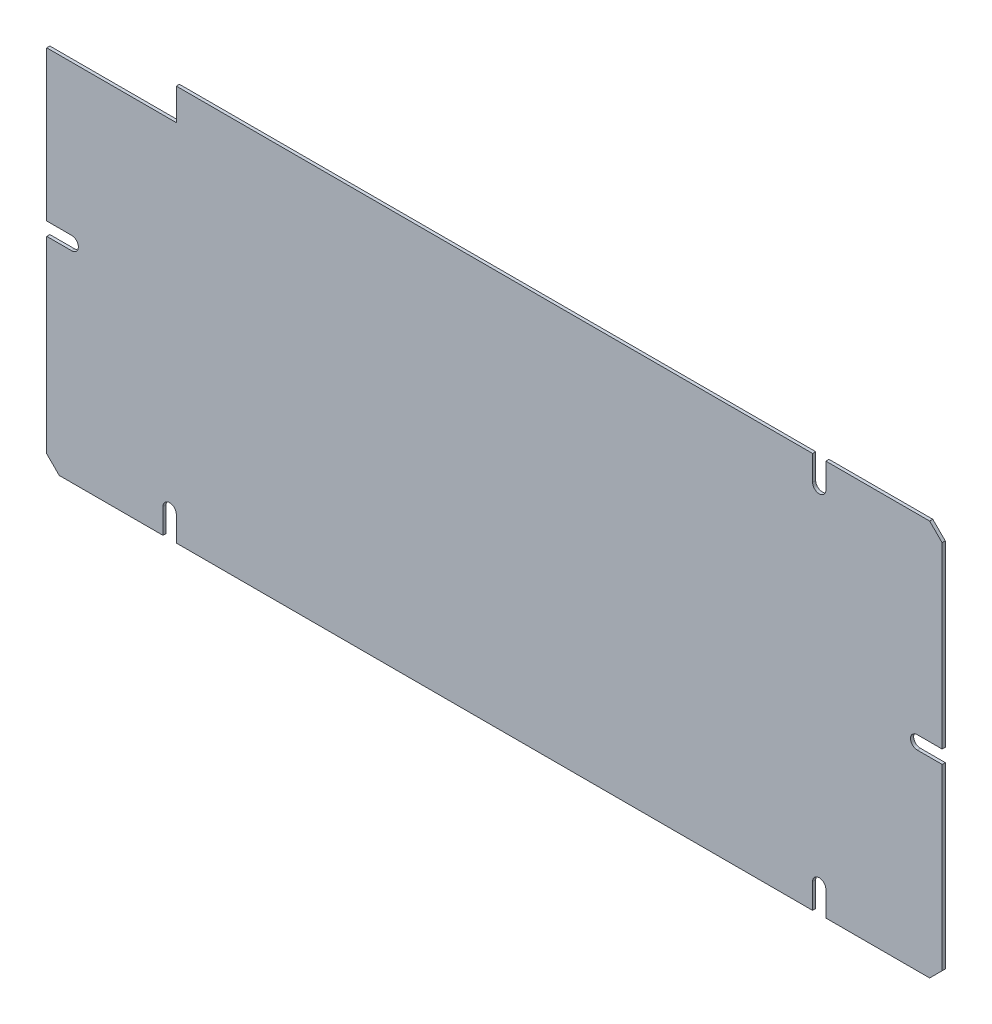
SolidWorks part; units mm, degrees
note: '?' marks a value the reader was unsure of.
material "PE High Density"
ref_plane "Front" through (0, 0, 0) normal (0, 0, 1) x (1, 0, 0)
ref_plane "Top" through (0, 0, 0) normal (0, 1, 0) x (1, 0, 0)
ref_plane "Right" through (0, 0, 0) normal (1, 0, 0) x (0, 0, -1)
ref_axis "Axis1" through (0, 0, 55) along (0, 0, -1)?
sketch "Sketch1" plane through (0, 0, 0) normal (0, 0, 1) x (1, 0, 0)
  line L1 (-227.584, 100.584) -> (227.584, 100.584)
  line L2 (-227.584, 100.584) -> (-227.584, -100.584)
  line L3 (-227.584, -100.584) -> (227.584, -100.584)
  line L4 (227.584, 100.584) -> (227.584, -100.584)
  line L5 (-227.584, 100.584) -> (227.584, -100.584) construction
  line L6 (-227.584, -100.584) -> (227.584, 100.584) construction
  point P0 (0, 0)
  dimension "D1" = 201.168
  dimension "D2" = 455.168
extrude "Boss-Extrude1" add sketch "Sketch1" along normal blind 1.5875
hole_wizard "1/4 Clearance Hole1" positions "Sketch2" profile "Sketch3" hole size "1/4" standard "ANSI Inch" end condition up to next
sketch "Sketch2" plane through (0, 0, 1.5875) normal (0, 0, 1) x (1, 0, 0)
  line L2 (-214.884, 87.884) -> (214.884, 87.884) construction
  line L3 (-214.884, 87.884) -> (-214.884, -87.884) construction
  line L4 (-214.884, -87.884) -> (214.884, -87.884) construction
  line L5 (214.884, 87.884) -> (214.884, -87.884) construction
  line L6 (-214.884, 87.884) -> (214.884, -87.884) construction
  line L7 (-214.884, -87.884) -> (214.884, 87.884) construction
  line L8 (-227.584, 100.584) -> (-227.584, -100.584) construction
  line L9 (227.584, 100.584) -> (-227.584, 100.584) construction
  line L10 (-227.584, -100.584) -> (227.584, -100.584) construction
  line L11 (227.584, -100.584) -> (227.584, 100.584) construction
  line L12 (-214.884, 0) -> (214.884, 0) construction
  line L14 (0, 87.884) -> (0, -87.884) construction
  line L15 (-165.1, 87.884) -> (-165.1, -87.884) construction
  line L17 (165.1, 87.884) -> (165.1, -87.884) construction
  point P0 (-165.1, 87.884)
  point P2 (165.1, 87.884)
  point P4 (214.884, 0)
  point P8 (-165.1, -87.884)
  point P10 (165.1, -87.884)
  point P224 (214.884, 0)
  point P245 (-214.884, 4.884)
  dimension "D1" = 12.7
  dimension "D2" = 12.7
  dimension "D3" = 12.7
  dimension "D4" = 12.7
  dimension "D5" = 330.2
sketch "Sketch3" plane through (-165.1, 87.884, 1.5875) normal (1, 0, 0) x (0, -1, 0)
  line L0 (0, 0) -> (0, 1.5875)
  line L1 (0, 1.5875) -> (3.3782, 1.5875)
  line L2 (3.3782, 1.5875) -> (3.3782, 0)
  line L5 (3.3782, 0) -> (0, 0)
  line L11 (0, -6.35) -> (0, 107.95) construction
  dimension "Thru Hole Dia." = 6.7564
  dimension "Thru Hole Depth" = 1.5875
hole_wizard "1/4 Clearance Slot1" [suppressed] positions "Sketch4" profile "Sketch5" size "1/4" standard "ANSI Inch"
sketch "Sketch4" plane through (0, 0, 1.5875) normal (0, 0, 1) x (1, 0, 0)
  line L0 (-47.5488, -87.884) -> (54.0512, -87.884) construction
  line L1 (3.2512, 87.884) -> (3.2512, -87.884) construction
  line L3 (227.584, 100.584) -> (-227.584, 100.584) construction
  line L4 (227.584, -100.584) -> (227.584, 100.584) construction
  point P0 (3.2512, -87.884)
  point P4 (3.2512, 87.884)
  dimension "D1" = 101.6
  dimension "D2" = 12.7
  dimension "D3" = 175.768
  dimension "D4" = 224.3328
sketch "Sketch5" plane through (3.2512, -87.884, 1.5875) normal (1, 0, 0) x (0, -1, 0)
  line L0 (0, 0) -> (0, 1.5875)
  line L1 (0, 1.5875) -> (3.3782, 1.5875)
  line L2 (3.3782, 1.5875) -> (3.3782, 0)
  line L5 (3.3782, 0) -> (0, 0)
  line L11 (0, -6.35) -> (0, 107.95) construction
  dimension "Thru Hole Dia." = 6.7564
  dimension "Thru Hole Depth" = 1.5875
sketch "Sketch6" plane through (0, 0, 1.5875) normal (0, 0, 1) x (1, 0, 0)
  line L0 (165.1, 91.2622) -> (165.1, 84.5058) construction
  line L1 (-168.4782, 87.884) -> (-161.7218, 87.884)
  line L2 (-168.4782, 87.884) -> (-168.4782, 102.362)
  line L3 (-168.4782, 102.362) -> (-161.7218, 102.362)
  line L4 (-161.7218, 87.884) -> (-161.7218, 102.362)
  line L5 (-168.4782, 87.884) -> (-161.7218, 102.362) construction
  line L6 (-168.4782, 102.362) -> (-161.7218, 87.884) construction
  line L7 (161.7218, 87.884) -> (168.4782, 87.884)
  line L8 (161.7218, 87.884) -> (161.7218, 102.362)
  line L9 (161.7218, 102.362) -> (168.4782, 102.362)
  line L10 (168.4782, 87.884) -> (168.4782, 102.362)
  line L11 (161.7218, 87.884) -> (168.4782, 102.362) construction
  line L12 (161.7218, 102.362) -> (168.4782, 87.884) construction
  line L13 (-165.1, 91.2622) -> (-165.1, 84.5058) construction
  circle A0 centre (-165.1, 87.884) radius 3.3782 construction
  circle A1 centre (165.1, 87.884) radius 3.3782 construction
  point P4 (-165.1, 95.123)
  point P11 (165.1, 95.123)
  point P17 (165.1, 87.884)
  point P18 (-165.1, 87.884)
  point P19 (165.1, 87.884)
  point P23 (-165.1, 87.884)
  dimension "D1" = 14.478
extrude "Cut-Extrude1" cut sketch "Sketch6" against normal up to next
mirror "Mirror1" about plane through (0, 0, 0) normal (0, 1, 0) of "Cut-Extrude1"
sketch "Sketch8" plane through (0, 0, 0) normal (0, 0, -1) x (-1, 0, 0)
  line L0 (227.584, 100.584) -> (227.584, -100.584) construction
  line L1 (168.4782, 100.584) -> (227.584, 100.584)
  line L3 (161.7218, 84.5058) -> (227.584, 84.5058)
  line L4 (227.584, 100.584) -> (227.584, 84.5058)
  line L5 (168.4782, 100.584) -> (227.584, 84.5058) construction
  line L6 (161.7218, 84.5058) -> (227.584, 100.584) construction
  line L9 (168.4782, 100.584) -> (161.7218, 100.584)
  line L10 (161.7218, 100.584) -> (161.7218, 84.5058)
  arc A1 (161.7218, 87.884) -> (168.4782, 87.884) centre (165.1, 87.884) ccw construction
  point P4 (196.4333, 92.9795)
sketch "Sketch7" plane through (0, 0, 1.5875) normal (0, 0, 1) x (1, 0, 0)
  line L0 (-214.884, 8.2622) -> (-227.584, 8.2622)
  line L1 (-227.584, 100.584) -> (-227.584, -100.584) construction
  line L6 (-227.584, 8.2622) -> (-227.584, 1.5058)
  line L7 (-227.584, 1.5058) -> (-214.884, 1.5058)
  line L8 (-214.884, 1.5058) -> (-214.884, 8.2622)
  line L9 (-218.2622, 4.884) -> (-211.5058, 4.884) construction
  line L10 (214.884, 3.3782) -> (214.884, -3.3782)
  line L11 (214.884, -3.3782) -> (227.584, -3.3782)
  line L12 (227.584, -100.584) -> (227.584, 100.584) construction
  line L13 (227.584, -3.3782) -> (227.584, 3.3782)
  line L14 (227.584, 3.3782) -> (214.884, 3.3782)
  circle A2 centre (-214.884, 4.884) radius 3.3782 construction
  circle A3 centre (214.884, 0) radius 3.3782 construction
  point P11 (-214.884, 4.884)
extrude "Cut-Extrude2" cut sketch "Sketch7" against normal up to next
extrude "Cut-Extrude3" cut sketch "Sketch8" against normal through all
chamfer "Chamfer1" distance 6.35 angle 45 3 edges at (-227.584, -100.584, 0.7937) (227.584, -100.584, 0.7937) (227.584, 100.584, 0.7937)
